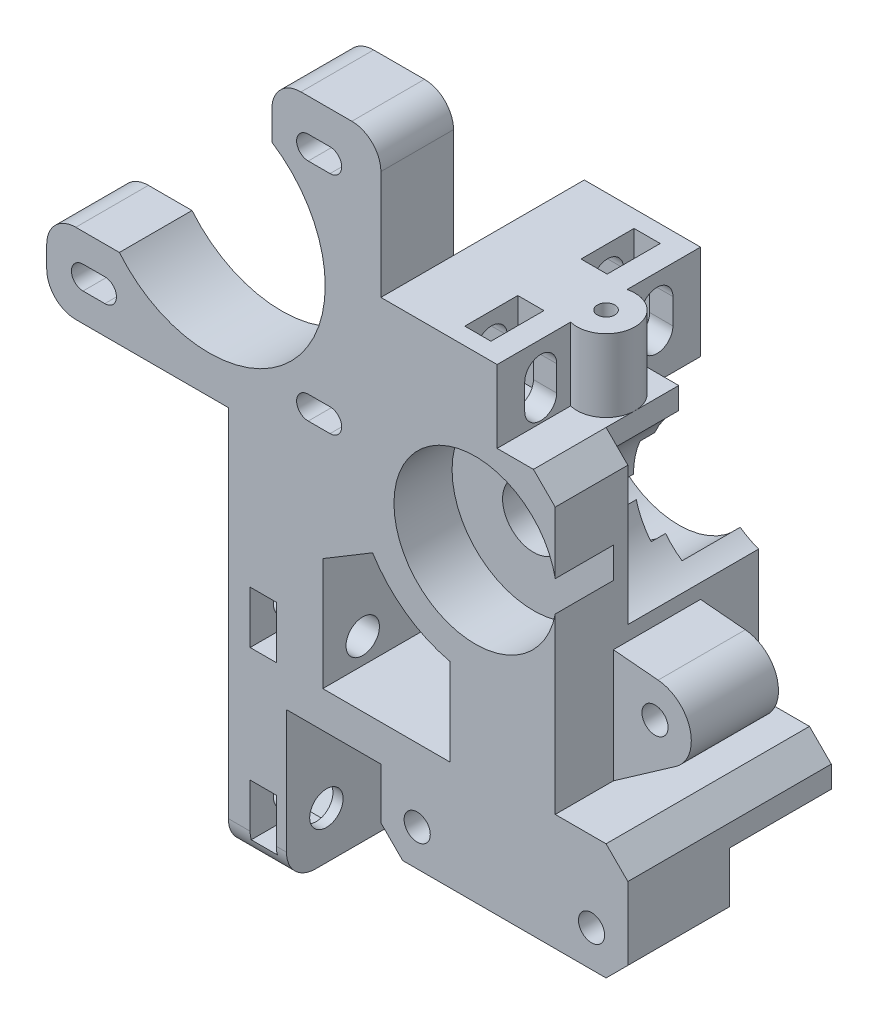
SolidWorks part; units mm, degrees
material "ABS"
ref_plane "Front Plane" through (0, 0, 0) normal (0, 0, 1) x (1, 0, 0)
ref_plane "Top Plane" through (0, 0, 0) normal (0, 1, 0) x (1, 0, 0)
ref_plane "Right Plane" through (0, 0, 0) normal (1, 0, 0) x (0, 0, -1)
sketch "Sketch1" plane through (0, 0, 0) normal (0, 0, 1) x (1, 0, 0)
  line L0 (0, 0) -> (0, -11)
  line L1 (0, -11) -> (25, -11)
  line L2 (25, -11) -> (25, -64)
  line L3 (25, -64) -> (33, -64)
  line L4 (33, -64) -> (33, -43)
  line L5 (33, -43) -> (46, -43)
  line L6 (46, -43) -> (46, -53)
  line L7 (46, -53) -> (85, -53)
  line L8 (85, -53) -> (85, -43) construction
  line L9 (85, -43) -> (80, -43)
  line L10 (80, -43) -> (80, -37)
  line L11 (80, -37) -> (70, -37)
  line L12 (70, -37) -> (78.6011, -30.9774)
  line L13 (70, -37) -> (70, -21.361) construction
  line L14 (70, -21.361) -> (76.169, -21.9007)
  line L15 (70, -21.361) -> (70, 12.639)
  line L16 (70, 12.639) -> (46, 12.639)
  line L17 (46, 12.639) -> (46, 31.639)
  line L18 (46, 31.639) -> (31, 31.639)
  line L19 (31, 31.639) -> (31, 23.639)
  line L20 (0, 0) -> (10, 0)
  line L21 (38, -22.5) -> (38, -38)
  line L22 (38, -38) -> (55.5, -38)
  line L23 (55.5, -38) -> (55.5, -26)
  line L24 (38, -22.5) -> (44.8573, -18.3797)
  line L25 (85, -48) -> (46, -48) construction
  line L26 (25, -11) -> (59, -11) construction
  line L27 (5, -5.5) -> (8, -5.5) construction
  line L28 (5, -3.9) -> (8, -3.9)
  line L29 (5, -7.1) -> (8, -7.1)
  line L30 (36, -5.5) -> (39, -5.5) construction
  line L31 (36, -3.9) -> (39, -3.9)
  line L32 (36, -7.1) -> (39, -7.1)
  line L33 (36, 25.5) -> (39, 25.5) construction
  line L34 (36, 27.1) -> (39, 27.1)
  line L35 (36, 23.9) -> (39, 23.9)
  line L36 (5, -5.5) -> (36, -5.5) construction
  line L37 (36, -5.5) -> (36, 25.5) construction
  line L38 (5, -5.5) -> (0, -5.5) construction
  arc A0 (85, -53) -> (85, -43) centre (85, -48) ccw
  circle A1 centre (75.7332, -26.8817) radius 5
  arc A2 (10, 0) -> (31, 23.639) centre (22.3388, 10.186) ccw
  arc A3 (44.8573, -18.3797) -> (55.5, -26) centre (59.3127, -9.4331) ccw
  circle A4 centre (51, -48) radius 1.8
  circle A5 centre (75, -48) radius 1.8
  circle A6 centre (85, -48) radius 1.8
  circle A7 centre (75.7332, -26.8817) radius 1.8
  circle A8 centre (59, -11) radius 4.25
  arc A9 (5, -3.9) -> (5, -7.1) centre (5, -5.5) ccw
  arc A10 (8, -7.1) -> (8, -3.9) centre (8, -5.5) ccw
  arc A11 (36, -3.9) -> (36, -7.1) centre (36, -5.5) ccw
  arc A12 (39, -7.1) -> (39, -3.9) centre (39, -5.5) ccw
  arc A13 (36, 27.1) -> (36, 23.9) centre (36, 25.5) ccw
  arc A14 (39, 23.9) -> (39, 27.1) centre (39, 25.5) ccw
  point P45 (6.5, -5.5)
  point P50 (37.5, -5.5)
  point P57 (37.5, 25.5)
  dimension "D1" = 11
  dimension "D14" = 35
  dimension "D9" = 10
  dimension "D15" = 10
  dimension "D21" = 10
  dimension "D28" = 17
  dimension "D31" = 3.6
  dimension "D33" = 24
  dimension "D34" = 34
  dimension "D35" = 8.5
  dimension "D37" = 1.6
  dimension "D39" = 5
  dimension "D40" = 16
  dimension "D2" = 25
  dimension "D4" = 8
  dimension "D5" = 21
  dimension "D6" = 13
  dimension "D7" = 10
  dimension "D8" = 39
  dimension "D10" = 5
  dimension "D11" = 6
  dimension "D12" = 10
  dimension "D13" = 10.5
  dimension "D16" = 40
  dimension "D17" = 34
  dimension "D18" = 24
  dimension "D19" = 19
  dimension "D20" = 15
  dimension "D22" = 8
  dimension "D23" = 15.5
  dimension "D24" = 17.5
  dimension "D25" = 12
  dimension "D26" = 8
  dimension "D27" = 121
  dimension "D29" = 5
  dimension "D30" = 5
  dimension "D32" = 5
  dimension "D36" = 3
  dimension "D38" = 31
  dimension "D41" = 53
extrude "Boss-Extrude1" add sketch "Sketch1" against normal blind 34 contours A2 L20 L0 L1 L2 L3 L4 L5 L6 L7 A0 L9 L10 L11 L12 A1 L14 L15 L16 L17 L18 L19 A14 L35 A13 L34 A12 L32 A11 L31 A10 L29 A9 L28 A8 A6 A5 A4 L24 A3 L23 L22 L21 | A1 A7 region at (48.0686, -19.084, 0) region at (79.3153, -23.5993, 0)
sketch "Sketch7" plane through (0, 0, 0) normal (0, 0, 1) x (1, 0, 0)
  line L1 (70, -21.361) -> (80.7332, -21.361)
  line L2 (70, -21.361) -> (70, -37)
  line L3 (70, -37) -> (80.7332, -37)
  line L4 (80.7332, -21.361) -> (80.7332, -37)
  circle A0 centre (59, -11) radius 11.2
  arc A1 (78.6011, -30.9774) -> (76.169, -21.9007) centre (75.7332, -26.8817) ccw construction
  dimension "D1" = 22.4
extrude "Cut-Extrude5" cut sketch "Sketch7" against normal blind 8
sketch "Sketch2" plane through (25, 0, 0) normal (-1, 0, 0) x (0, 0, 1)
  line L0 (-28.5, -34.5) -> (-5.5, -34.5) construction
  line L1 (-5.5, -34.5) -> (-5.5, -57.5) construction
  line L2 (-5.5, -57.5) -> (-28.5, -57.5) construction
  line L3 (-28.5, -57.5) -> (-28.5, -34.5) construction
  line L4 (-17, -57.5) -> (-17, -64) construction
  line L5 (-34, -64) -> (0, -64) construction
  line L6 (-34, -24) -> (-28, -24)
  line L7 (-34, -11) -> (-34, -64) construction
  line L8 (-28, -24) -> (-28, 13.5)
  line L9 (-28, 13.5) -> (-10, 13.5)
  line L10 (-10, 13.5) -> (-10, 31.639)
  line L11 (-34, 31.639) -> (0, 31.639) construction
  line L12 (-10, 31.639) -> (-34, 31.639)
  line L13 (-34, 31.639) -> (-34, -24)
  circle A0 centre (-28.5, -34.5) radius 2.3
  circle A1 centre (-5.5, -34.5) radius 2.3
  circle A2 centre (-5.5, -57.5) radius 2.3
  circle A3 centre (-28.5, -57.5) radius 2.3
  dimension "D3" = 4.6
  dimension "D1" = 23
  dimension "D2" = 6.5
  dimension "D4" = 6
  dimension "D5" = 37.5
  dimension "D6" = 18
  dimension "D7" = 40
extrude "Cut-Extrude1" cut sketch "Sketch2" against normal blind 28
sketch "Sketch4" plane through (0, 0, -34) normal (0, 0, -1) x (-1, 0, 0)
  line L0 (-25, -24) -> (-46, -11.3806)
  line L1 (-46, -11.3806) -> (-46, 31.639)
  line L2 (-46, 31.639) -> (0, 31.639)
  line L3 (0, 31.639) -> (0, -11)
  line L4 (0, -11) -> (-25, -11)
  line L5 (-25, -11) -> (-25, -24)
  line L6 (-70, 12.639) -> (-67, 12.639)
  line L7 (-46, -53) -> (-85, -53) construction
  line L8 (-70, 12.639) -> (-70, -19.361)
  line L9 (-70, -21.361) -> (-70, 12.639) construction
  line L10 (-80, -43) -> (-90, -43)
  line L11 (-67, 12.639) -> (-67, -0.361)
  line L12 (-80, -43) -> (-80, -53)
  line L13 (-80, -53) -> (-90, -53)
  line L14 (-90, -43) -> (-90, -53)
  arc A0 (-70, -19.361) -> (-67, -0.361) centre (-73.7732, -9.0284) ccw
  arc A1 (-85, -43) -> (-85, -53) centre (-85, -48) ccw construction
  dimension "D4" = 11
  dimension "D1" = 24.5
  dimension "D2" = 3
  dimension "D3" = 32
  dimension "D5" = 13
extrude "Cut-Extrude2" cut sketch "Sketch4" against normal blind 24
sketch "Sketch5" plane through (0, 0, -34) normal (0, 0, -1) x (-1, 0, 0)
  line L0 (-33, -24) -> (-33, -64)
  line L1 (-25, -24) -> (-38, -24) construction
  line L2 (-33, -24) -> (0, -24)
  line L3 (0, -24) -> (0, 31.639)
  line L4 (0, 31.639) -> (-90, 31.639)
  line L5 (-90, 31.639) -> (-90, -64)
  line L6 (-90, -64) -> (-33, -64)
  line L7 (-46, 31.639) -> (-31, 31.639) construction
  line L9 (-25, -64) -> (-33, -64) construction
  line L10 (-33, -64) -> (-33, -43) construction
  arc A0 (-85, -43) -> (-85, -53) centre (-85, -48) ccw construction
extrude "Cut-Extrude3" cut sketch "Sketch5" against normal blind 6 contours L5 L6 L0 L2 L3 L4
sketch "Sketch6" plane through (0, 0, -34) normal (0, 0, -1) x (-1, 0, 0)
  line L0 (-67, 12.639) -> (-67, -3.4502)
  line L1 (-70, -21.361) -> (-80.7332, -21.361)
  line L2 (-70, -21.361) -> (-70, -37)
  line L3 (-70, -37) -> (-80.7332, -37)
  line L4 (-80.7332, -21.361) -> (-80.7332, -37)
  line L5 (-67, -0.361) -> (-67, 12.639) construction
  line L6 (-67, 12.639) -> (-62, 12.639)
  line L7 (-46, 12.639) -> (-67, 12.639) construction
  line L8 (-62, 12.639) -> (-62, -0.417)
  circle A0 centre (-59, -11) radius 11
  arc A1 (-76.169, -21.9007) -> (-78.6011, -30.9774) centre (-75.7332, -26.8817) ccw construction
  dimension "D1" = 22
  dimension "D2" = 5
extrude "Cut-Extrude4" cut sketch "Sketch6" against normal blind 14 contours A0 L8 L6 L0 | A0 | L1 L4 L3 L2 region at (64.5868, 5.4811, -34) region at (59, -11, -34) region at (75.3666, -29.1805, -34)
sketch "Sketch8" plane through (0, 0, -28) normal (0, 0, -1) x (-1, 0, 0)
  line L1 (-46, -53) -> (-80, -53)
  line L2 (-46, -53) -> (-46, -43)
  line L3 (-46, -43) -> (-80, -43)
  line L4 (-80, -53) -> (-80, -43)
extrude "Cut-Extrude7" cut sketch "Sketch8" against normal blind 14
sketch "Sketch9" plane through (0, 0, -20) normal (0, 0, -1) x (-1, 0, 0)
  circle A0 centre (-59, -11) radius 7.9
  dimension "D1" = 15.8
extrude "Cut-Extrude8" cut sketch "Sketch9" against normal blind 2
sketch "Sketch10" plane through (0, 12.639, 0) normal (0, 1, 0) x (1, 0, 0)
  line L0 (70, 10) -> (70, 0)
  line L1 (70, 8) -> (70, 0) construction
  line L2 (57, 2.35) -> (57, 0) construction
  line L3 (55.2, 25.65) -> (58.8, 25.65)
  line L4 (55.2, 25.65) -> (55.2, 18.35)
  line L5 (55.2, 18.35) -> (58.8, 18.35)
  line L6 (58.8, 25.65) -> (58.8, 18.35)
  line L7 (55.2, 9.65) -> (58.8, 9.65)
  line L8 (55.2, 9.65) -> (55.2, 2.35)
  line L9 (55.2, 2.35) -> (58.8, 2.35)
  line L10 (58.8, 9.65) -> (58.8, 2.35)
  line L11 (57, 25.65) -> (57, 28) construction
  line L12 (57, 9.65) -> (57, 18.35) construction
  line L14 (70, 0) -> (46, 0) construction
  line L15 (70, 10) -> (67, 10)
  line L16 (67, 10) -> (67, 20)
  line L17 (67, 20) -> (62, 20)
  line L18 (67.4569, 20) -> (48, 20) construction
  line L19 (62, 20) -> (62, 17.873)
  line L20 (62, 17.873) -> (62, 10.127) construction
  line L21 (63, 14) -> (57, 14) construction
  line L22 (70, 0) -> (62, 0)
  line L23 (62, 0) -> (62, 10.127)
  line L24 (46, 28) -> (62, 28) construction
  arc A0 (62, 17.873) -> (62, 10.127) centre (63, 14) cw
  line M9 (67, 20) -> (62, 20)
  line M15 (70, 0) -> (70, 10)
  line M16 (70, 10) -> (67, 10)
  line M17 (67, 10) -> (67, 20)
  dimension "D5" = 4
  dimension "D2" = 7.3
  dimension "D3" = 3.6
  dimension "D4" = 2.35
  dimension "D6" = 5
extrude "Cut-Extrude9" cut sketch "Sketch10" against normal blind 10 contours L6 L3 L4 L5 | L19 A0 L16 M9 | A0 L23 L22 M17 M15 M16 | L8 L9 L10 L7 region at (64.9023, 12.639, -18.5143) region at (66.0025, 12.639, -5.245) region at (57, 12.639, -22)
sketch "Sketch11" plane through (0, -53, 0) normal (0, -1, 0) x (1, 0, 0)
  line L0 (46, -14) -> (80, -14) construction
  circle A0 centre (63, -14) radius 1.2
  dimension "D1" = 2.4
extrude "Cut-Extrude10" cut sketch "Sketch11" against normal through all both and the other way through all
sketch "Sketch12" plane through (0, -53, 0) normal (0, -1, 0) x (1, 0, 0)
  circle A0 centre (63, -14) radius 8.1
  dimension "D1" = 16.2
extrude "Cut-Extrude11" cut sketch "Sketch12" against normal up to surface (10 mm away) from offset 6 up to face at (55.5, -43, -14.15) offset against normal yes
sketch "Sketch13" plane through (0, -53, 0) normal (0, -1, 0) x (1, 0, 0)
  circle A0 centre (63, -14) radius 6.1
  dimension "D1" = 12.2
extrude "Cut-Extrude12" cut sketch "Sketch13" against normal up to surface (6 mm away) up to face at (63, -47, -11.675)
sketch "Sketch15" plane through (62, 0, 0) normal (1, 0, 0) x (0, 0, -1)
  line L0 (6, 8.639) -> (6, 5.139) construction
  line L1 (8.2, 8.639) -> (8.2, 5.139)
  line L2 (3.8, 8.639) -> (3.8, 5.139)
  line L3 (22, 8.639) -> (22, 5.139) construction
  line L4 (24.2, 8.639) -> (24.2, 5.139)
  line L5 (19.8, 8.639) -> (19.8, 5.139)
  line L6 (6, 6.889) -> (22, 6.889) construction
  line L7 (6, 8.639) -> (6, 12.639) construction
  line L9 (10, 12.639) -> (0, 12.639) construction
  line L10 (10, 12.639) -> (10, 2.639) construction
  arc A0 (8.2, 8.639) -> (3.8, 8.639) centre (6, 8.639) ccw
  arc A1 (3.8, 5.139) -> (8.2, 5.139) centre (6, 5.139) ccw
  arc A2 (24.2, 8.639) -> (19.8, 8.639) centre (22, 8.639) ccw
  arc A3 (19.8, 5.139) -> (24.2, 5.139) centre (22, 5.139) ccw
  point P2 (6, 6.889)
  point P11 (22, 6.889)
  dimension "D2" = 2.2
  dimension "D1" = 3.5
  dimension "D3" = 4
  dimension "D4" = 16
  dimension "D5" = 4
extrude "Cut-Extrude14" cut sketch "Sketch15" against normal up to surface (16 mm away) up to face at (46, 0.6292, -19)
ref_plane "Plane1" through (28, 0, 0) normal (-1, 0, 0) x (0, 0, 1)
sketch "Sketch16" plane through (28, 0, 0) normal (-1, 0, 0) x (0, 0, 1)
  line L0 (-30.5785, -53.9) -> (-34, -53.9)
  line L1 (-24.3431, -34.5) -> (-26.4215, -30.9)
  line L2 (-26.4215, -30.9) -> (-30.5785, -30.9)
  line L3 (-30.5785, -30.9) -> (-32.6569, -34.5)
  line L4 (-32.6569, -34.5) -> (-30.5785, -38.1)
  line L5 (-30.5785, -38.1) -> (-26.4215, -38.1)
  line L6 (-26.4215, -38.1) -> (-24.3431, -34.5)
  line L7 (-24.3431, -57.5) -> (-26.4215, -53.9)
  line L8 (-26.4215, -53.9) -> (-30.5785, -53.9)
  line L9 (-30.5785, -53.9) -> (-32.6569, -57.5)
  line L10 (-32.6569, -57.5) -> (-30.5785, -61.1)
  line L11 (-30.5785, -61.1) -> (-26.4215, -61.1)
  line L12 (-26.4215, -61.1) -> (-24.3431, -57.5)
  line L13 (-9.6569, -57.5) -> (-7.5785, -61.1)
  line L14 (-7.5785, -61.1) -> (-3.4215, -61.1)
  line L15 (-3.4215, -61.1) -> (-1.3431, -57.5)
  line L16 (-1.3431, -57.5) -> (-3.4215, -53.9)
  line L17 (-3.4215, -53.9) -> (-7.5785, -53.9)
  line L18 (-7.5785, -53.9) -> (-9.6569, -57.5)
  line L19 (-9.6569, -34.5) -> (-7.5785, -38.1)
  line L20 (-7.5785, -38.1) -> (-3.4215, -38.1)
  line L21 (-3.4215, -38.1) -> (-1.3431, -34.5)
  line L22 (-1.3431, -34.5) -> (-3.4215, -30.9)
  line L23 (-3.4215, -30.9) -> (-7.5785, -30.9)
  line L24 (-7.5785, -30.9) -> (-9.6569, -34.5)
  line L25 (-34, -24) -> (-34, -64) construction
  line L26 (-34, -53.9) -> (-34, -61.1)
  line L27 (-34, -61.1) -> (-30.5785, -61.1)
  line L28 (-30.5785, -30.9) -> (-34, -30.9)
  line L29 (-34, -30.9) -> (-34, -38.1)
  line L30 (-34, -38.1) -> (-30.5785, -38.1)
  line L31 (-3.4215, -30.9) -> (0, -30.9)
  line L32 (0, -11) -> (0, -64) construction
  line L33 (0, -30.9) -> (0, -38.1)
  line L34 (0, -38.1) -> (-3.4215, -38.1)
  line L35 (-3.4215, -53.9) -> (0, -53.9)
  line L36 (0, -53.9) -> (0, -61.1)
  line L37 (0, -61.1) -> (-3.4215, -61.1)
  circle A0 centre (-28.5, -34.5) radius 3.6 construction
  circle A1 centre (-28.5, -57.5) radius 3.6 construction
  circle A2 centre (-5.5, -57.5) radius 3.6 construction
  circle A3 centre (-5.5, -34.5) radius 3.6 construction
  dimension "D1" = 7.2
extrude "Cut-Extrude15" cut sketch "Sketch16" against normal blind 3.6 contours L29 L30 L4 L3 L28 | L5 L6 L1 L2 L3 L4 | L26 L27 L10 L9 L0 | L11 L12 L7 L8 L9 L10 | L23 L24 L19 L20 L21 L22 | L34 L33 L31 L22 L21 | L17 L18 L13 L14 L15 L16 | L37 L36 L35 L16 L15 region at (28, -57.5, -32.7333) region at (28, -57.5, -28.5) region at (28, -34.5, -28.5) region at (28, -34.5, -32.7333) region at (28, -57.5, -5.5) region at (28, -57.5, -1.2667) region at (28, -34.5, -5.5) region at (28, -34.5, -1.2667)
fillet "Fillet1" radius 4 7 edges at (31, 31.639, -5) (46, 31.639, -5) (0, 0, -5) (0, -11, -5) (29, -24, -34) (29, -64, -34) (29, -64, 0)
sketch "Sketch17" plane through (0, 0, -10) normal (0, 0, -1) x (-1, 0, 0)
  line L0 (-80, -43) -> (-85, -43) construction
  line L1 (-80, -53) -> (-90, -53)
  line L2 (-80, -53) -> (-80, -43)
  line L3 (-80, -43) -> (-90, -43)
  line L4 (-90, -53) -> (-90, -43)
  arc A0 (-85, -43) -> (-85, -53) centre (-85, -48) ccw construction
extrude "fail" cut sketch "Sketch17" against normal through all both and the other way through all
chamfer "Chamfer1" distance 3 angle 45 4 edges at (46, -53, -7) (80, -53, -7) (70, 2.639, -5) (80, -37, -14)
